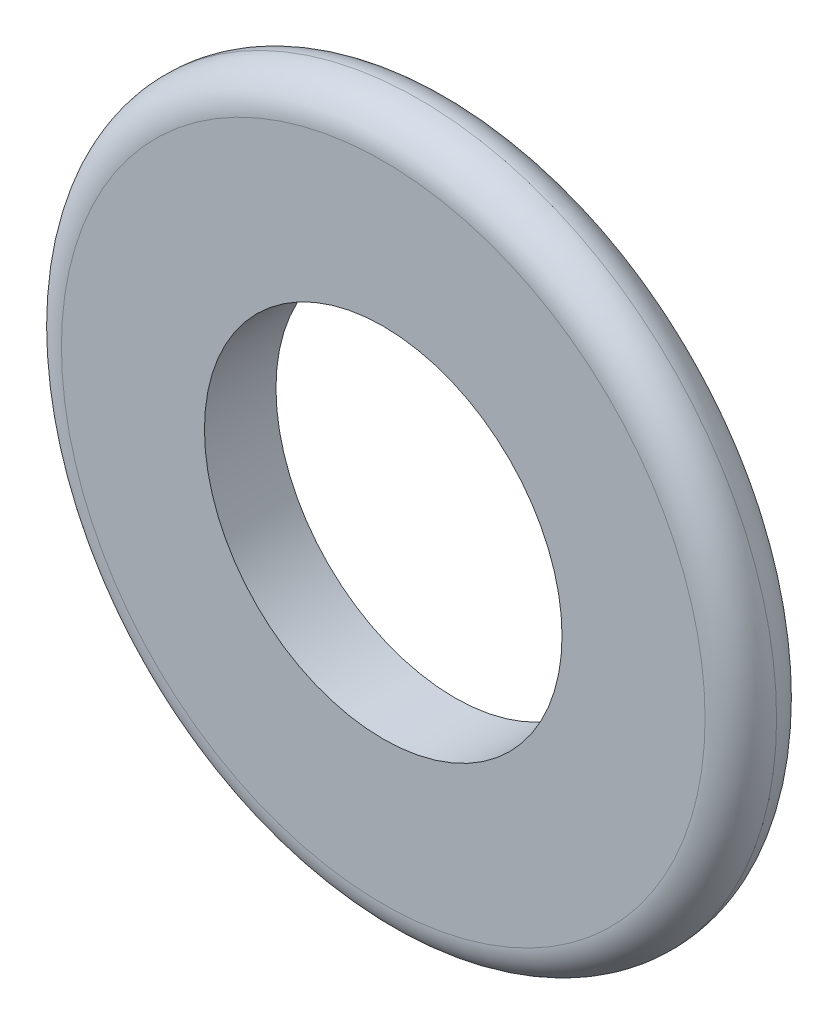
SolidWorks part; units mm, degrees
ref_plane "Front Plane" through (0, 0, 0) normal (0, 0, 1) x (1, 0, 0)
ref_plane "Top Plane" through (0, 0, 0) normal (0, 1, 0) x (1, 0, 0)
ref_plane "Right Plane" through (0, 0, 0) normal (1, 0, 0) x (0, 0, -1)
sketch "Sketch1" plane through (0, 0, 0) normal (0, 0, 1) x (1, 0, 0)
  circle A0 centre (0, 0) radius 5
  circle A1 centre (0, 0) radius 2.5
  dimension "D1" = 10
  dimension "D2" = 5
extrude "Boss-Extrude1" add sketch "Sketch1" along normal blind 1
fillet "Fillet2" radius 0.5 2 edges at (5, 0, 0) (5, 0, 1)
